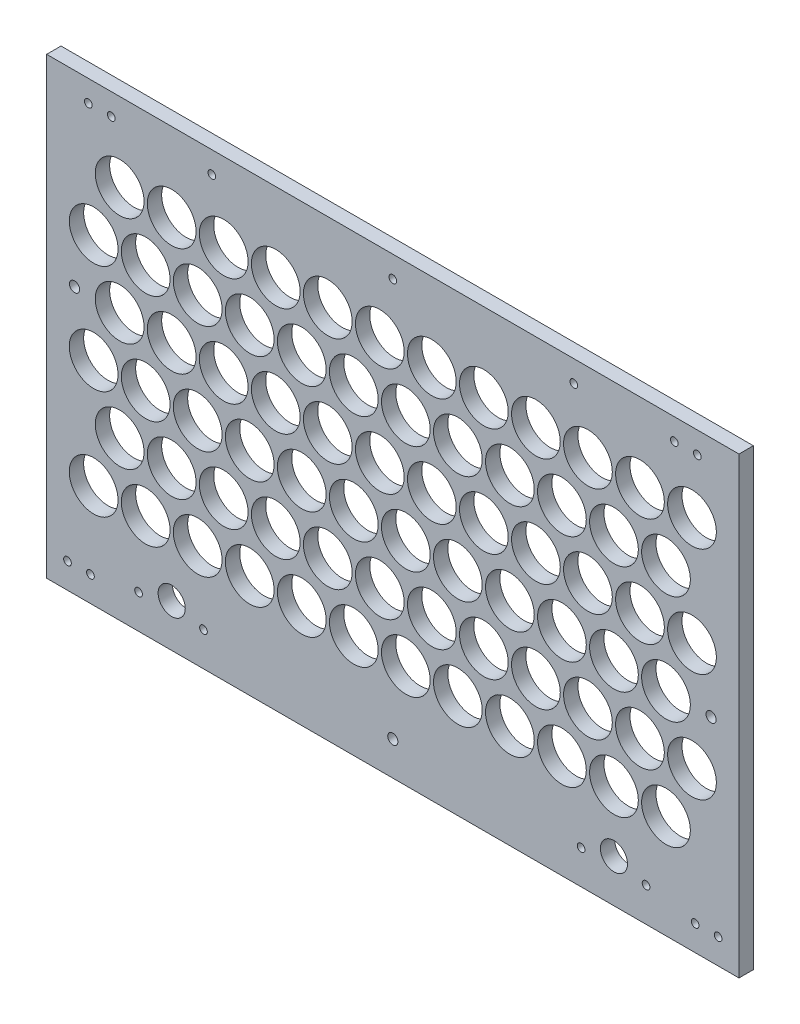
SolidWorks part; units mm, degrees
material "ABS"
ref_plane "X-Y Datum" through (0, 0, 0) normal (0, 0, 1) x (1, 0, 0)
ref_plane "X-Z Datum" through (0, 0, 0) normal (0, 1, 0) x (1, 0, 0)
ref_plane "Y-Z Datum" through (0, 0, 0) normal (1, 0, 0) x (0, 0, -1)
sketch "Sketch1" plane through (0, 0, 0) normal (0, 0, 1) x (1, 0, 0)
  line L1 (-143.025, 70.775) -> (143.025, 70.775)
  line L2 (-143.025, 70.775) -> (-143.025, -70.775)
  line L3 (-143.025, -70.775) -> (143.025, -70.775)
  line L4 (143.025, 70.775) -> (143.025, -70.775)
  line L5 (-143.025, 70.775) -> (143.025, -70.775) construction
  line L6 (-143.025, -70.775) -> (143.025, 70.775) construction
  line L13 (-153.025, -105.775) -> (153.025, -105.775)
  line L14 (-153.025, 91.65) -> (153.025, 91.65)
  line L15 (-153.025, 91.65) -> (-153.025, -105.775)
  line L16 (153.025, 91.65) -> (153.025, -105.775)
  line L17 (153.025, 70.775) -> (153.025, -70.775) construction
  line L18 (-143.025, 91.65) -> (143.025, 91.65) construction
  line L19 (-143.025, -105.775) -> (143.025, -105.775) construction
  line L20 (-153.025, 70.775) -> (-153.025, -70.775) construction
  line L21 (-132.25, -60) -> (-109.25, -60) construction
  circle A0 centre (-132.25, -60) radius 10.775
  circle A1 centre (-109.25, -60) radius 10.775 construction
  circle A2 centre (-120.75, -36) radius 10.775
  point P0 (0, 0)
  point P16 (-120.75, -60)
  dimension "D1" = 21.55
  dimension "D2" = 23
  dimension "D3" = 24
  dimension "D5" = 141.55
  dimension "D6" = 286.05
  dimension "D7" = 35
  dimension "D8" = 20.875
  dimension "D9" = 10
  dimension "D10" = 10
extrude "Boss-Extrude1" add sketch "Sketch1" along normal blind 6.35 contours A0 L3 L4 L1 L2 A2 | A2 | A0 | A0 L2 L3 | L1 L4 L3 L2 region at (2.4105, 0.9241, 0) region at (-140.6182, -68.3682, 0) region at (-132.25, -60, 0) region at (-149.383, -7.0625, 0) region at (-120.75, -36, 0)
sketch "Sketch3" plane through (0, 0, 6.35) normal (0, 0, 1) x (1, 0, 0)
  line L4 (143.025, 70.775) -> (-143.025, 70.775)
  line L5 (143.025, -70.775) -> (143.025, 70.775)
  line L6 (-143.025, -70.775) -> (143.025, -70.775)
  line L7 (-143.025, 70.775) -> (-143.025, -70.775)
  line L8 (143.025, 70.775) -> (-143.025, 70.775)
  line L9 (143.025, -70.775) -> (143.025, 70.775)
  line L10 (-143.025, -70.775) -> (143.025, -70.775)
  line L11 (-143.025, 70.775) -> (-143.025, -70.775)
  circle A1 centre (-120.75, -36) radius 10.775
  circle A2 centre (-120.75, -36) radius 10.775
  circle A3 centre (-132.25, -60) radius 10.775
  circle A4 centre (-132.25, -60) radius 10.775
  dimension "D1" = 0
  dimension "D2" = 0
  dimension "D3" = 0
extrude "Cut-Extrude1" cut sketch "Sketch3" against normal through all contours A4 region at (-132.25, -60, 6.35)
sketch "Sketch4" plane through (0, 0, 6.35) normal (0, 0, 1) x (1, 0, 0)
  line L4 (143.025, 70.775) -> (-143.025, 70.775)
  line L5 (143.025, -70.775) -> (143.025, 70.775)
  line L6 (-143.025, -70.775) -> (143.025, -70.775)
  line L7 (-143.025, 70.775) -> (-143.025, -70.775)
  line L8 (143.025, 70.775) -> (-143.025, 70.775)
  line L9 (143.025, -70.775) -> (143.025, 70.775)
  line L10 (-143.025, -70.775) -> (143.025, -70.775)
  line L11 (-143.025, 70.775) -> (-143.025, -70.775)
  circle A1 centre (-120.75, -36) radius 10.775
  circle A2 centre (-120.75, -36) radius 10.775
  circle A3 centre (-132.25, -60) radius 10.775
  circle A4 centre (-132.25, -60) radius 10.775
  dimension "D1" = 0
  dimension "D2" = 0
  dimension "D3" = 0
extrude "Cut-Extrude2" cut sketch "Sketch4" against normal through all contours A2 region at (-120.75, -36, 6.35)
pattern_linear "LPattern1" count 12 spacing 23 along (1, 0, 0) of "Cut-Extrude1", "Cut-Extrude2"
pattern_linear "LPattern2" count 3 spacing 48 along (0, 1, 0) of "LPattern1"
sketch "Sketch5" plane through (0, 0, 0) normal (0, 0, -1) x (-1, 0, 0)
sketch "Sketch13" plane through (0, 91.65, 0) normal (0, 1, 0) x (1, 0, 0)
  line L4 (153.025, 0) -> (-153.025, 0)
  line L5 (-153.025, 0) -> (-153.025, -6.35)
  line L6 (-153.025, -6.35) -> (153.025, -6.35)
  line L7 (153.025, -6.35) -> (153.025, 0)
  line L8 (153.025, 0) -> (-153.025, 0)
  line L9 (-153.025, 0) -> (-153.025, -6.35)
  line L10 (-153.025, -6.35) -> (153.025, -6.35)
  line L11 (153.025, -6.35) -> (153.025, 0)
  dimension "D1" = 0
extrude "Boss-Extrude2" add sketch "Sketch13" along normal blind 3.175
sketch "Sketch14" plane through (0, 0, 0) normal (0, 0, -1) x (-1, 0, 0)
  circle A0 centre (-97.75, -86.775) radius 6
  point P6 (0, 0)
extrude "Cut-Extrude3" cut sketch "Sketch14" against normal through all
mirror "Mirror1" about plane through (0, 0, 0) normal (1, 0, 0) of "Cut-Extrude3"
sketch "Sketch15" plane through (0, 0, 0) normal (0, 0, -1) x (-1, 0, 0)
  point P0 (-111.94, -90.775)
  point P1 (-83.25, -90.775)
  point P3 (83.712, -90.775)
  point P5 (112.402, -90.775)
  point P7 (134.61, 85.3)
  point P9 (124.45, 85.3)
  point P11 (80, 85.3)
  point P13 (0, 85.3)
  point P15 (-80, 85.3)
  point P17 (-124.45, 85.3)
  point P19 (-134.61, 85.3)
  point P21 (0, 0)
  point P25 (143.8175, -94.6)
  point P27 (133.6575, -94.6)
  point P29 (-133.6575, -94.6)
  point P31 (-143.8175, -94.6)
  point P33 (0, 0)
hole_wizard "M3 Clearance Hole1" positions "Sketch15" profile "Sketch16" hole size "M3" standard "ANSI Metric" end condition through all
sketch "Sketch16" plane through (111.94, -90.775, 0) normal (1, 0, 0) x (0, 1, 0)
  line L0 (0, 0) -> (0, 6.35)
  line L1 (0, 6.35) -> (1.7, 6.35)
  line L2 (1.7, 6.35) -> (1.7, 0)
  line L5 (1.7, 0) -> (0, 0)
  line L11 (0, -6.35) -> (0, 107.95) construction
  dimension "Thru Hole Dia." = 3.4
  dimension "Thru Hole Depth" = 6.35
sketch "Sketch17" plane through (0, 0, 0) normal (0, 0, -1) x (-1, 0, 0)
  line L0 (0, -105.775) -> (0, -77.9164) construction
  line L1 (153.025, -105.775) -> (-153.025, -105.775) construction
  circle A0 centre (0, -90.775) radius 2.25
  circle A1 centre (140.6875, 12) radius 2.25
  circle A2 centre (-140.6875, -12) radius 2.25
  point P0 (-140.6875, -12)
  point P1 (140.6875, 12)
  point P9 (0, -90.775)
  point P11 (83.712, -90.775)
  dimension "D1" = 4.5
extrude "Cut-Extrude4" cut sketch "Sketch17" against normal through all
